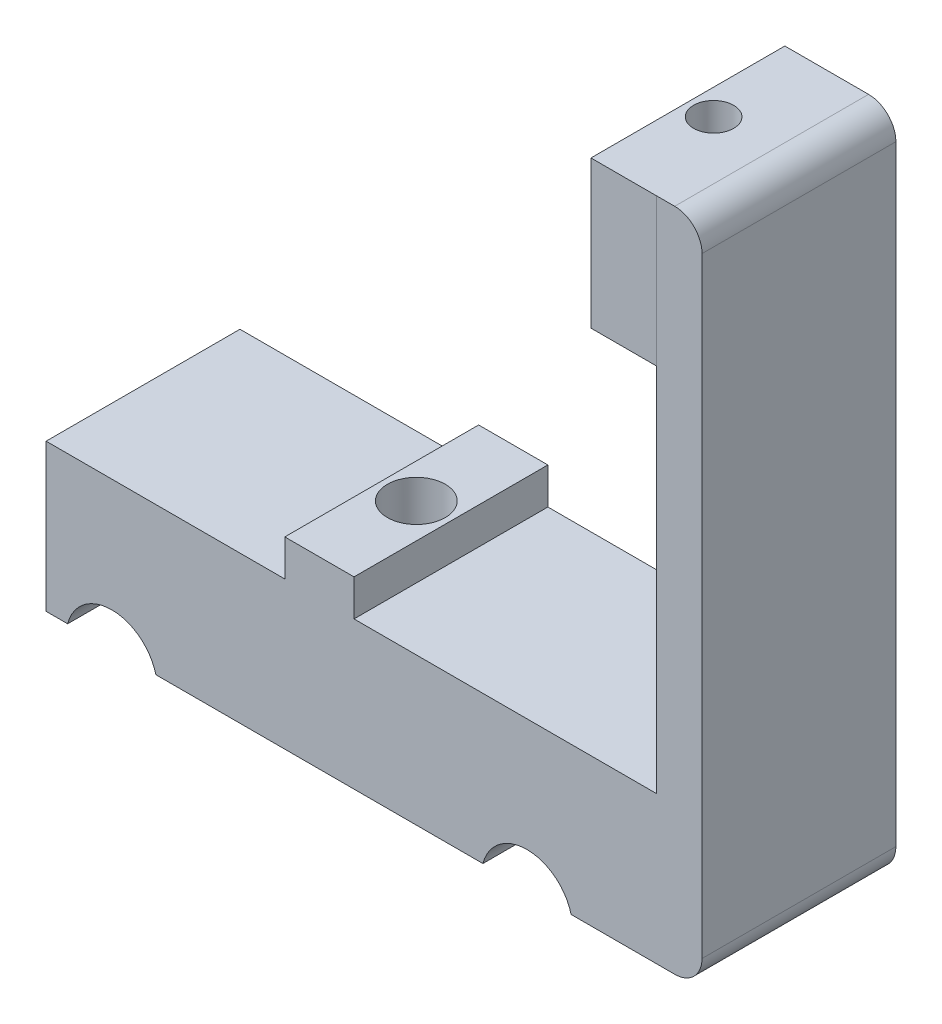
SolidWorks part; units mm, degrees
ref_plane "Front Plane" through (0, 0, 0) normal (0, 0, 1) x (1, 0, 0)
ref_plane "Top Plane" through (0, 0, 0) normal (0, 1, 0) x (1, 0, 0)
ref_plane "Right Plane" through (0, 0, 0) normal (1, 0, 0) x (0, 0, -1)
sketch "Sketch2" plane through (0, 0, 0) normal (0, 0, 1) x (1, 0, 0)
  line L0 (10.1, 0) -> (-10.1, 0)
  line L1 (-10.1, 0) -> (-10.1, 1.7099)
  line L2 (-10.1, 1.7099) -> (-6.2548, 7)
  line L3 (-6.2548, 7) -> (6.2548, 7)
  line L4 (0, 7) -> (0, 0)
  line L5 (0, 0) -> (0, 9.2516) construction
  line L6 (10.1, 1.7099) -> (6.2548, 7)
  line L7 (10.1, 0) -> (10.1, 1.7099)
  dimension "D1" = 20.2
  dimension "D2" = 7
extrude "Boss-Extrude1" add sketch "Sketch2" along normal blind 10.8 contours L4 L3 L2 L1 L0 | L0 L7 L6 L3 L4 region at (4.4168, 3.2082, 0) region at (-4.4168, 3.2082, 0)
sketch "Sketch4" plane through (0, 0, 0) normal (0, 0, 1) x (1, 0, 0)
  line L0 (-3.8, 0) -> (-3.8, -4.8)
  line L1 (10.1, 0) -> (-10.1, 0) construction
  line L2 (-3.8, -4.8) -> (-30, -4.8)
  line L3 (-30, -4.8) -> (-30, -29.8)
  line L4 (-30, -29.8) -> (30, -29.8)
  line L5 (0, 0) -> (0, -29.8) construction
  line L6 (0, -29.8) -> (0, 0)
  line L7 (3.8, 0) -> (-3.8, 0)
  line L8 (0, 0) -> (0, -30.5381) construction
  line L9 (30, -4.8) -> (30, -29.8)
  line L10 (3.8, -4.8) -> (30, -4.8)
  line L11 (3.8, 0) -> (3.8, -4.8)
  line L13 (-30, -20.98) -> (30, -20.98)
  line L14 (-30, -20.98) -> (-30, -23.48)
  line L15 (-30, -23.48) -> (30, -23.48)
  line L16 (30, -20.98) -> (30, -23.48)
  dimension "D1" = 4.8
  dimension "D2" = 3.8
  dimension "D3" = 25
  dimension "D4" = 60
  dimension "D6" = 8.82
extrude "Boss-Extrude2" add sketch "Sketch4" along normal mid plane 21.28 contours L6 L7 L0 L2 L3 L4 | L11 L7 L6 L4 L9 L10 region at (-14.5256, -12.5101, 0) region at (14.5256, -12.5101, 0)
sketch "Sketch5" plane through (0, 0, 0) normal (0, 0, 1) x (1, 0, 0)
  line L0 (-29.791, -22.2274) -> (26.9734, -22.2274) construction
  line L3 (0, -20.98) -> (0, 7) construction
  line L5 (-6.2548, 7) -> (6.2548, 7) construction
  line L20 (-30, -20.98) -> (30, -20.98) construction
  circle A0 centre (-22.791, -22.2274) radius 5
  circle A1 centre (22.791, -22.2274) radius 5
  dimension "D1" = 7
extrude "Cut-Extrude1" cut sketch "Sketch5" along normal through all both and the other way through all
fillet "Fillet1" radius 1 6 edges at (-10.1, 0, 5.4) (-10.1, 1.7099, 5.4) (-6.2548, 7, 5.4) (6.2548, 7, 5.4) (10.1, 0, 5.4) (10.1, 1.7099, 5.4)
sketch "Sketch6" plane through (30, 0, 0) normal (1, 0, 0) x (0, 0, -1)
  line L0 (-10.64, -20.98) -> (10.64, -20.98) construction
  line L1 (-10.64, -4.8) -> (10.64, -4.8)
  line L2 (-10.64, -4.8) -> (-10.64, -20.98)
  line L3 (-10.64, -20.98) -> (10.64, -20.98)
  line L4 (10.64, -4.8) -> (10.64, -20.98)
extrude "Boss-Extrude3" add sketch "Sketch6" along normal blind 12
sketch "Sketch7" plane through (0, -4.8, 0) normal (0, 1, 0) x (1, 0, 0)
  line L0 (3.8, -10.64) -> (42, -10.64) construction
  line L1 (42, 10.6413) -> (37, 10.6413)
  line L2 (42, 10.6413) -> (42, -10.64)
  line L3 (42, -10.64) -> (37, -10.64)
  line L4 (37, 10.6413) -> (37, -10.64)
  dimension "D1" = 5
extrude "Boss-Extrude4" add sketch "Sketch7" along normal blind 56.83
sketch "Sketch8" plane through (37, 0, 0) normal (-1, 0, 0) x (0, 0, 1)
  line L0 (-10.6413, 52.03) -> (-10.6413, -4.8) construction
  line L1 (10.643, 52.03) -> (-10.6413, 52.03)
  line L2 (10.643, 52.03) -> (10.643, 35.85)
  line L3 (10.643, 35.85) -> (-10.6413, 35.85)
  line L4 (-10.6413, 52.03) -> (-10.6413, 35.85)
  dimension "D1" = 16.18
extrude "Boss-Extrude5" add sketch "Sketch8" along normal blind 7.19
fillet "Fillet3" radius 3 2 edges at (42, 52.03, -0.0007) (42, -20.98, 0)
sketch "Sketch9" plane through (0, -20.98, 0) normal (0, -1, 0) x (1, 0, 0)
  line L0 (27.6329, 0) -> (27.6329, 10.8) construction
  line L2 (27.6329, 10.64) -> (39, 10.64) construction
  circle A0 centre (32.6329, 0) radius 2.2
  dimension "D1" = 5
  dimension "D2" = 10.64
extrude "Cut-Extrude2" cut sketch "Sketch9" against normal through all
sketch "Sketch10" plane through (0, -20.98, 0) normal (0, -1, 0) x (1, 0, 0)
  line L2 (-17.9491, 0) -> (-17.9491, 10.8) construction
  line L3 (-17.9491, 10.64) -> (17.9491, 10.64) construction
  circle A0 centre (0.0009, 0) radius 3.175
  dimension "D1" = 10.64
  dimension "D3" = 6.35
  dimension "D2" = 17.95
extrude "Cut-Extrude3" cut sketch "Sketch10" against normal through all
sketch "Sketch11" plane through (0, 0, 10.8) normal (0, 0, 1) x (1, 0, 0)
  line L0 (9.1, 0) -> (-9.1, 0) construction
  line L1 (-12.6098, 8.9215) -> (12.3675, 8.9215)
  line L2 (-12.6098, 8.9215) -> (-12.6098, -0.8)
  line L3 (-12.6098, -0.8) -> (12.3675, -0.8)
  line L4 (12.3675, 8.9215) -> (12.3675, -0.8)
  dimension "D1" = 0.8
extrude "Cut-Extrude4" cut sketch "Sketch11" against normal through all
